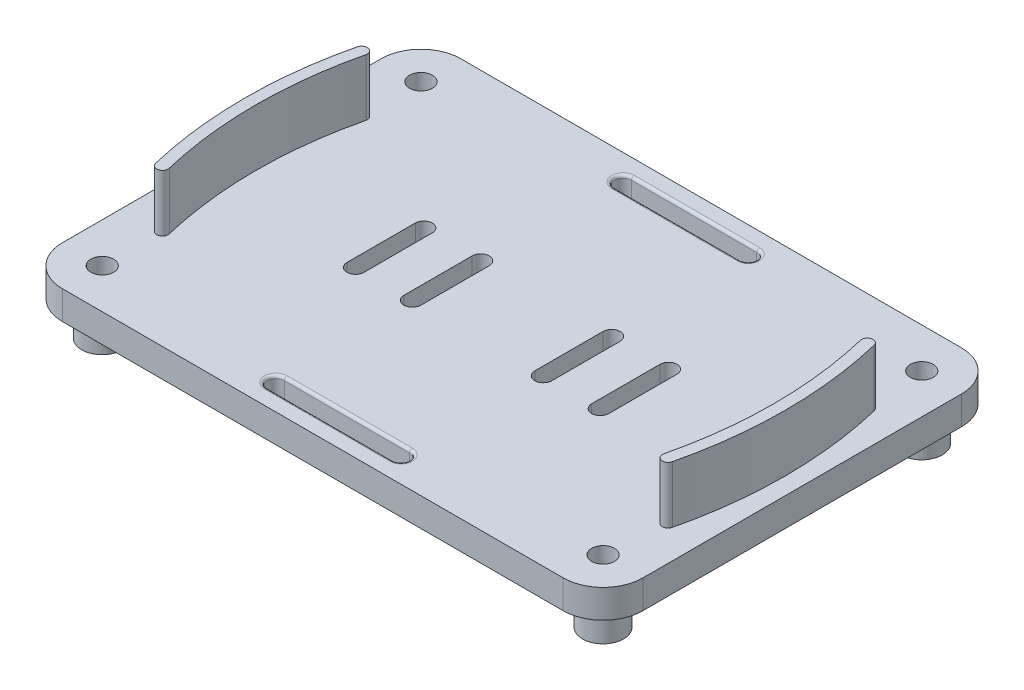
SolidWorks part; units mm, degrees
material "ABS PC"
ref_plane "Front Plane" through (0, 0, 0) normal (0, 0, 1) x (1, 0, 0)
ref_plane "Top Plane" through (0, 0, 0) normal (0, 1, 0) x (1, 0, 0)
ref_plane "Right Plane" through (0, 0, 0) normal (1, 0, 0) x (0, 0, -1)
sketch "Sketch1" plane through (0, 0, 0) normal (0, 1, 0) x (1, 0, 0)
  line L1 (-44, -35) -> (44, -35)
  line L2 (-51, -28) -> (-51, 28)
  line L3 (-44, 35) -> (44, 35)
  line L4 (51, -28) -> (51, 28)
  line L5 (-51, -35) -> (51, 35) construction
  line L6 (-51, 35) -> (51, -35) construction
  arc A0 (44, 35) -> (51, 28) centre (44, 28) cw
  arc A1 (44, -35) -> (51, -28) centre (44, -28) ccw
  arc A2 (-44, -35) -> (-51, -28) centre (-44, -28) cw
  arc A3 (-51, 28) -> (-44, 35) centre (-44, 28) cw
  point P0 (0, 0)
  dimension "D3" = 7
  dimension "D1" = 102
  dimension "D2" = 70
extrude "Boss-Extrude1" add sketch "Sketch1" along normal blind 5 contours L3 A0 L4 A1 L1 A2 L2 A3
sketch "Sketch2" plane through (0, 5, 0) normal (0, 1, 0) x (1, 0, 0)
  line L4 (-11, -30.5) -> (11, -30.5) construction
  line L5 (-11, -29) -> (11, -29)
  line L6 (-11, -32) -> (11, -32)
  line L7 (-44, -35) -> (44, -35) construction
  line L8 (-11.5, 6) -> (-11.5, -6) construction
  line L10 (0, -87.4721) -> (0, 26.4721) construction
  line L11 (-29.5651, 0) -> (32.1867, 0) construction
  line L18 (-11, 30.5) -> (11, 30.5) construction
  line L19 (-11, 29) -> (11, 29)
  line L20 (-11, 32) -> (11, 32)
  line L21 (-21.5, 6) -> (-21.5, -6) construction
  line L22 (-20, 6) -> (-20, -6)
  line L23 (-23, 6) -> (-23, -6)
  line L24 (-10, 6) -> (-10, -6)
  line L25 (-13, 6) -> (-13, -6)
  line L26 (11.5, 6) -> (11.5, -6) construction
  line L27 (10, 6) -> (10, -6)
  line L28 (13, 6) -> (13, -6)
  line L29 (21.5, 6) -> (21.5, -6) construction
  line L30 (20, 6) -> (20, -6)
  line L31 (23, 6) -> (23, -6)
  arc A0 (-11, -29) -> (-11, -32) centre (-11, -30.5) ccw
  arc A1 (11, -32) -> (11, -29) centre (11, -30.5) ccw
  arc A6 (-11, 29) -> (-11, 32) centre (-11, 30.5) cw
  arc A7 (11, 32) -> (11, 29) centre (11, 30.5) cw
  arc A8 (-20, 6) -> (-23, 6) centre (-21.5, 6) ccw
  arc A9 (-23, -6) -> (-20, -6) centre (-21.5, -6) ccw
  arc A10 (-10, 6) -> (-13, 6) centre (-11.5, 6) ccw
  arc A11 (-13, -6) -> (-10, -6) centre (-11.5, -6) ccw
  arc A12 (10, 6) -> (13, 6) centre (11.5, 6) cw
  arc A13 (13, -6) -> (10, -6) centre (11.5, -6) cw
  arc A14 (20, 6) -> (23, 6) centre (21.5, 6) cw
  arc A15 (23, -6) -> (20, -6) centre (21.5, -6) cw
  point P2 (0, -30.5)
  point P32 (0, 30.5)
  point P39 (-21.5, 0)
  point P46 (-11.5, 0)
  point P54 (11.5, 0)
  point P61 (21.5, 0)
  dimension "D1" = 25
  dimension "D5" = 15
  dimension "D2" = 3
  dimension "D3" = 3
  dimension "D6" = 3
  dimension "D7" = 20
  dimension "D8" = 10
extrude "Cut-Extrude1" cut sketch "Sketch2" against normal blind 12
sketch "Sketch3" plane through (0, 5, 0) normal (0, 1, 0) x (1, 0, 0)
  line L0 (-51, -28) -> (-51, 28) construction
  line L2 (51, -28) -> (51, 28) construction
  arc A0 (-43.9298, 17.5) -> (-43.9298, -17.5) centre (29, 0) ccw construction
  arc A1 (-44.9022, 17.7333) -> (-44.9022, -17.7333) centre (29, 0) ccw
  arc A2 (-42.9574, 17.2667) -> (-42.9574, -17.2667) centre (29, 0) ccw
  arc A3 (-44.9022, 17.7333) -> (-42.9574, 17.2667) centre (-43.9298, 17.5) cw
  arc A4 (-44.9022, -17.7333) -> (-42.9574, -17.2667) centre (-43.9298, -17.5) ccw
  arc A5 (44.9298, 17.5) -> (44.9298, -17.5) centre (-28, 0) cw construction
  arc A6 (43.9574, 17.2667) -> (43.9574, -17.2667) centre (-28, 0) cw
  arc A7 (45.9022, 17.7333) -> (45.9022, -17.7333) centre (-28, 0) cw
  arc A8 (43.9574, 17.2667) -> (45.9022, 17.7333) centre (44.9298, 17.5) cw
  arc A9 (43.9574, -17.2667) -> (45.9022, -17.7333) centre (44.9298, -17.5) ccw
  point P7 (-46, 0)
  point P18 (47, 0)
  dimension "D2" = 75
  dimension "D3" = 35
  dimension "D6" = 35
  dimension "D7" = 4
  dimension "D8" = 75
  dimension "D1" = 5
  dimension "D4" = 1
  dimension "D5" = 1
  dimension "D9" = 1
  dimension "D10" = 1
extrude "Boss-Extrude2" add sketch "Sketch3" along normal blind 10
fillet "Fillet1" radius 0.5 16 edges at (0, 0, -29) (12.5, 0, -30.5) (0, 0, -32) (12.5, 0, 30.5) (0, 0, 29) (-12.5, 0, 30.5) (12.5, 5, 30.5) (0, 5, 32) (-12.5, 5, 30.5) (12.5, 5, -30.5) (0, 5, -29) (-12.5, 5, -30.5) (-12.5, 0, -30.5) (0, 0, 32) (0, 5, 29) (0, 5, -32)
sketch "Sketch4" plane through (0, 5, 0) normal (0, 1, 0) x (1, 0, 0)
  circle A0 centre (-44, 28) radius 3.6
  circle A1 centre (-44, -28) radius 3.6
  circle A2 centre (44, -28) radius 3.6
  circle A3 centre (44, 28) radius 3.6
  point P0 (-44, 28)
  dimension "D1" = 7.2
extrude "Boss-Extrude3" add sketch "Sketch4" against normal blind 6 from surface starting at face at (0, 0, -30.5)
sketch "Sketch6" plane through (0, 5, 0) normal (0, 1, 0) x (1, 0, 0)
  line L0 (-5.067, 0) -> (5.6178, 0) construction
  circle A0 centre (-44, 28) radius 2
  circle A1 centre (44, 28) radius 2
  circle A2 centre (44, -28) radius 2
  circle A3 centre (-44, -28) radius 2
  dimension "D1" = 4
extrude "Cut-Extrude2" cut sketch "Sketch6" against normal through all
